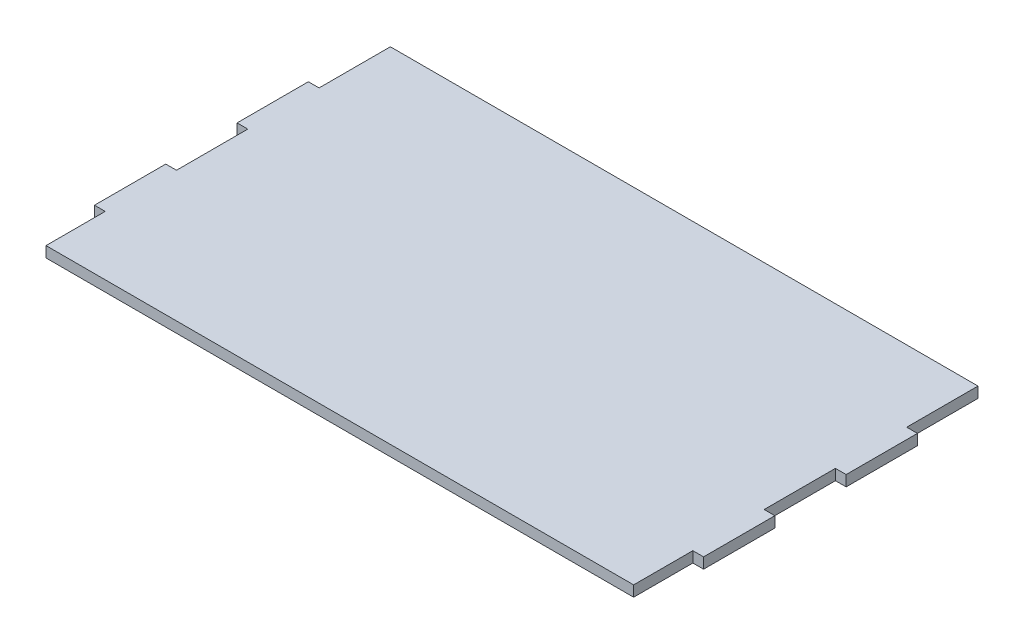
SolidWorks part; units mm, degrees
ref_plane "Ön Düzlem" through (0, 0, 0) normal (0, 0, 1) x (1, 0, 0)
ref_plane "Üst Düzlem" through (0, 0, 0) normal (0, 1, 0) x (1, 0, 0)
ref_plane "Sağ Düzlem" through (0, 0, 0) normal (1, 0, 0) x (0, 0, -1)
sketch "Sketch2" plane through (0, 0, 0) normal (0, 1, 0) x (1, 0, 0)
  line L0 (-76.7, -26.931) -> (-76.7, -8.977)
  line L3 (74, 44.885) -> (-74, 44.885)
  line L6 (-74, -41.845) -> (74, -41.845)
  line L8 (-76.7, 8.977) -> (-76.7, 26.931)
  line L10 (-76.7, 26.931) -> (-74, 26.931)
  line L11 (-74, 8.977) -> (-74, -8.977)
  line L12 (-74, 26.931) -> (-74, 44.885)
  line L13 (-76.7, 8.977) -> (-74, 8.977)
  line L14 (-76.7, -26.931) -> (-74, -26.931)
  line L15 (-76.7, -8.977) -> (-74, -8.977)
  line L16 (-74, -26.931) -> (-74, -41.845)
  line L17 (76.7, -26.931) -> (76.7, -8.977)
  line L19 (76.7, 8.977) -> (76.7, 26.931)
  line L21 (74, -26.931) -> (74, -41.845)
  line L22 (74, 44.885) -> (74, 26.931)
  line L23 (76.7, -26.931) -> (74, -26.931)
  line L24 (76.7, -8.977) -> (74, -8.977)
  line L25 (76.7, 8.977) -> (74, 8.977)
  line L26 (76.7, 26.931) -> (74, 26.931)
  line L27 (74, 8.977) -> (74, -8.977)
  point P0 (0, 0)
extrude "Boss-Extrude1" add sketch "Sketch2" along normal blind 2.7
